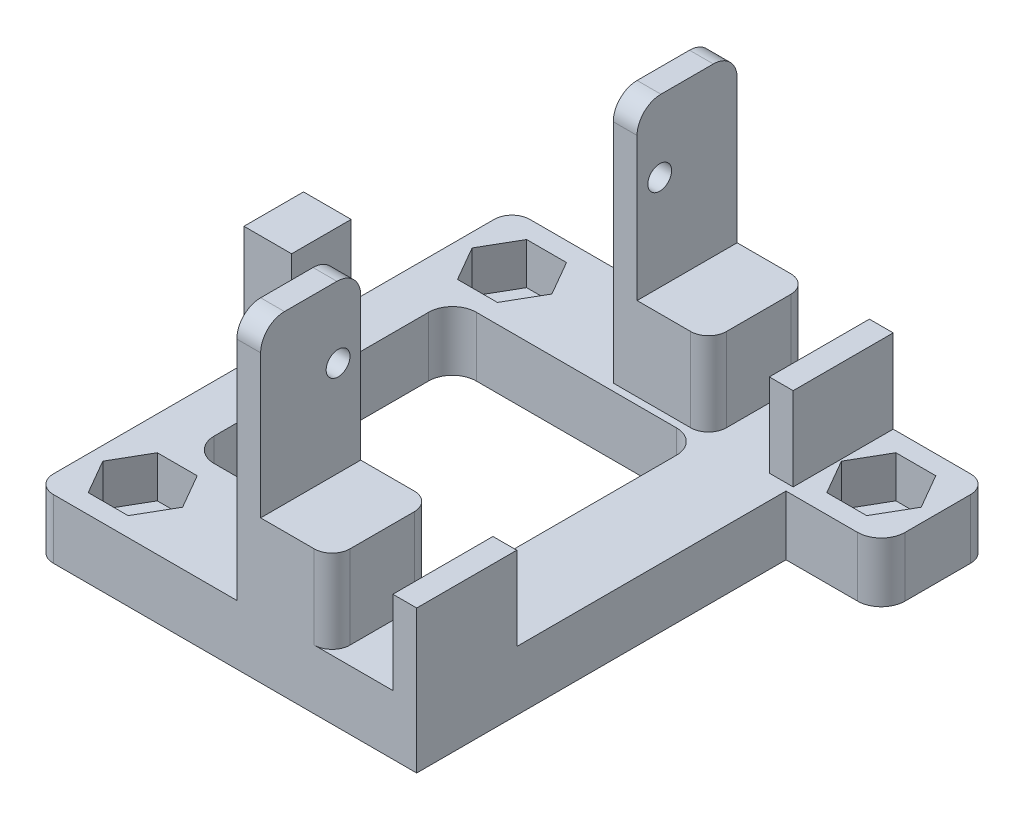
SolidWorks part; units mm, degrees
ref_plane "Plan de face" through (0, 0, 0) normal (0, 0, 1) x (1, 0, 0)
ref_plane "Plan de dessus" through (0, 0, 0) normal (0, 1, 0) x (1, 0, 0)
ref_plane "Plan de droite" through (0, 0, 0) normal (1, 0, 0) x (0, 0, -1)
sketch "Esquisse1" plane through (0, 0, 0) normal (0, 1, 0) x (1, 0, 0)
  circle A0 centre (0, 0) radius 11.75
  dimension "D1" = 23.5
extrude "Boss.-Extru.1" add sketch "Esquisse1" along normal blind 0.0001
sketch "Esquisse2" plane through (0, 0.0001, 0) normal (0, 1, 0) x (1, 0, 0)
  line L1 (-20, -20) -> (20, -20)
  line L2 (-20, -20) -> (-20, 20)
  line L3 (-20, 20) -> (20, 20)
  line L4 (20, -20) -> (20, 20)
  line L5 (-20, -20) -> (20, 20) construction
  line L6 (-20, 20) -> (20, -20) construction
  point P0 (0, 0)
  dimension "D1" = 40
  dimension "D2" = 40
extrude "Boss.-Extru.2" add sketch "Esquisse2" along normal blind 5
sketch "Esquisse3" plane through (0, 5.0001, 0) normal (0, 1, 0) x (1, 0, 0)
  line L0 (-15.5, 15.5) -> (15.5, 15.5) construction
  line L1 (15.5, 15.5) -> (15.5, -15.5) construction
  line L2 (0, 0) -> (-15.5, 0) construction
  line L4 (15.5, -15.5) -> (-15.5, -15.5) construction
  line L6 (-15.5, -15.5) -> (-15.5, 15.5) construction
  line L8 (0, 15.5) -> (0, 0) construction
  line L13 (-13.8257, 12.6) -> (-12.1514, 15.5)
  line L14 (-12.1514, 15.5) -> (-13.8257, 18.4)
  line L15 (-13.8257, 18.4) -> (-17.1743, 18.4)
  line L16 (-17.1743, 18.4) -> (-18.8486, 15.5)
  line L17 (-18.8486, 15.5) -> (-17.1743, 12.6)
  line L18 (-17.1743, 12.6) -> (-13.8257, 12.6)
  line L19 (-18.8486, -15.5) -> (-17.1743, -18.4)
  line L20 (-17.1743, -18.4) -> (-13.8257, -18.4)
  line L21 (-13.8257, -18.4) -> (-12.1514, -15.5)
  line L22 (-12.1514, -15.5) -> (-13.8257, -12.6)
  line L23 (-13.8257, -12.6) -> (-17.1743, -12.6)
  line L24 (-17.1743, -12.6) -> (-18.8486, -15.5)
  line L25 (12.1514, -15.5) -> (13.8257, -18.4)
  line L26 (13.8257, -18.4) -> (17.1743, -18.4)
  line L27 (17.1743, -18.4) -> (18.8486, -15.5)
  line L28 (18.8486, -15.5) -> (17.1743, -12.6)
  line L29 (17.1743, -12.6) -> (13.8257, -12.6)
  line L30 (13.8257, -12.6) -> (12.1514, -15.5)
  line L31 (13.8257, 12.6) -> (17.1743, 12.6)
  line L32 (17.1743, 12.6) -> (18.8486, 15.5)
  line L33 (18.8486, 15.5) -> (17.1743, 18.4)
  line L34 (17.1743, 18.4) -> (13.8257, 18.4)
  line L35 (13.8257, 18.4) -> (12.1514, 15.5)
  line L36 (12.1514, 15.5) -> (13.8257, 12.6)
  circle A4 centre (-15.5, 15.5) radius 2.9 construction
  circle A5 centre (-15.5, -15.5) radius 2.9 construction
  circle A6 centre (15.5, -15.5) radius 2.9 construction
  circle A7 centre (15.5, 15.5) radius 2.9 construction
  point P3 (-13.8931, -18)
  point P5 (-12.6132, -15.5)
  point P6 (12.6132, -15.5)
  point P7 (12.6132, 15.5)
  point P9 (-12.6132, 15.5)
  dimension "D7" = 5.8
  dimension "D8" = 5.8
  dimension "D9" = 5.8
  dimension "D10" = 5.8
  dimension "D2" = 31
  dimension "D3" = 31
  dimension "D4" = 90
  dimension "D5" = 90
extrude "Enlèv. mat.-Extru.1" cut sketch "Esquisse3" against normal blind 3.5
sketch "Esquisse4" plane through (0, 1.5001, 0) normal (0, 1, 0) x (1, 0, 0)
  line L0 (-13.8257, 18.4) -> (-17.1743, 12.6) construction
  line L1 (13.8257, 18.4) -> (17.1743, 12.6) construction
  line L2 (-17.1743, -18.4) -> (-13.8257, -12.6) construction
  line L3 (13.8257, -12.6) -> (17.1743, -18.4) construction
  circle A0 centre (-15.5, 15.5) radius 1.75
  circle A1 centre (15.5, 15.5) radius 1.75
  circle A2 centre (-15.5, -15.5) radius 1.75
  circle A3 centre (15.5, -15.5) radius 1.75
  dimension "D1" = 3.5
  dimension "D2" = 3.5
  dimension "D3" = 3.5
  dimension "D4" = 3.5
extrude "Enlèv. mat.-Extru.2" cut sketch "Esquisse4" against normal blind 2
sketch "Esquisse5" plane through (0, 5.0001, 0) normal (0, 1, 0) x (1, 0, 0)
  line L0 (20, 10.013) -> (12, 10.013) construction
  line L1 (20, -20) -> (20, 20) construction
  line L2 (12, 20) -> (12, -20)
  line L3 (20, 20) -> (-20, 20) construction
  line L4 (-20, -20) -> (20, -20) construction
  line L5 (12, -20) -> (10, -20)
  line L6 (10, -20) -> (10, 20)
  line L7 (10, 20) -> (12, 20)
  line L8 (4.9, 20) -> (-3.1, 20)
  line L9 (-3.1, 20) -> (-3.1, -20)
  line L10 (-3.1, -20) -> (4.9, -20)
  line L11 (4.9, -20) -> (4.9, 20)
  dimension "D1" = 8
  dimension "D2" = 2
  dimension "D3" = 5.1
  dimension "D4" = 8
extrude "Boss.-Extru.3" add sketch "Esquisse5" along normal blind 7
sketch "Esquisse6" plane through (0, 12.0001, 0) normal (0, 1, 0) x (1, 0, 0)
  line L0 (-3.1, -20) -> (4.9, -20) construction
  line L1 (-3.1, 20) -> (-1.1, 20)
  line L2 (-3.1, 20) -> (-3.1, -20)
  line L3 (-3.1, -20) -> (-1.1, -20)
  line L4 (-1.1, 20) -> (-1.1, -20)
  dimension "D1" = 2
extrude "Boss.-Extru.4" add sketch "Esquisse6" along normal blind 14
sketch "Esquisse7" plane through (-1.1, 0, 0) normal (1, 0, 0) x (0, 0, -1)
  line L0 (0, 26.0001) -> (0, 20.0001) construction
  line L1 (-20, 26.0001) -> (20, 26.0001) construction
  line L2 (0, 20.0001) -> (-13.5, 20.0001) construction
  line L3 (0, 20.0001) -> (13.5, 20.0001) construction
  line L4 (0, 26.0001) -> (-11.6, 26.0001)
  line L5 (-11.6, 26.0001) -> (-11.6, 5.0001)
  line L6 (-11.6, 5.0001) -> (11.6, 5.0001)
  line L7 (11.6, 5.0001) -> (11.6, 26.0001)
  line L8 (11.6, 26.0001) -> (0, 26.0001)
  circle A0 centre (-13.5, 20.0001) radius 1
  circle A1 centre (13.5, 20.0001) radius 1
  point P8 (0, 20.0001)
  dimension "D3" = 2
  dimension "D4" = 2
  dimension "D1" = 13.5
  dimension "D2" = 6
  dimension "D5" = 13.5
  dimension "D6" = 11.6
  dimension "D7" = 11.6
  dimension "D8" = 21
extrude "Enlèv. mat.-Extru.3" cut sketch "Esquisse7" against normal blind 14 and the other way blind 14 contours A0 | A1 | L8 L4 L5 L6 L7 region at (-1.1, 20.0001, 13.5) region at (-1.1, 20.0001, -13.5)
fillet "Congé1" radius 2 4 edges at (-2.1, 26.0001, 20) (-2.1, 26.0001, 11.6) (-2.1, 26.0001, -20) (-2.1, 26.0001, -11.6)
fillet "Congé2" radius 1.5 4 edges at (4.9, 8.5001, -20) (4.9, 8.5001, -11.6) (4.9, 8.5001, 11.6) (4.9, 8.5001, 20)
fillet "Congé3" radius 1.5 4 edges at (20, 2.5001, -20) (20, 2.5001, 20) (-20, 2.5001, -20) (-20, 2.5001, 20)
sketch "Esquisse10" plane through (0, 5.0001, 0) normal (0, 1, 0) x (1, 0, 0)
  line L0 (20, -18.5) -> (20, 18.5) construction
  line L1 (12, -20) -> (20, -20)
  line L2 (12, -20) -> (12, 11)
  line L3 (12, 11) -> (20, 11)
  line L4 (20, -20) -> (20, 11)
  dimension "D1" = 31
extrude "Enlèv. mat.-Extru.4" cut sketch "Esquisse10" against normal blind 10
fillet "Congé4" radius 2 1 edges at (20, 2.5001, -11)
sketch "Esquisse11" plane through (0, 5.0001, 0) normal (0, 1, 0) x (1, 0, 0)
  line L0 (-20, 3.0994) -> (-16, 3.0994) construction
  line L1 (-16, -11) -> (4.8, -11)
  line L2 (-16, -11) -> (-16, 11)
  line L3 (-16, 11) -> (4.8, 11)
  line L4 (4.8, -11) -> (4.8, 11)
  line L5 (-20, 18.5) -> (-20, -18.5) construction
  line L6 (-9.2703, 11) -> (-9.2703, 20) construction
  line L8 (4.8, 15.8) -> (10, 15.8)
  line L9 (10, 20) -> (10, 11.6) construction
  line L10 (-3.1, 20) -> (-18.5, 20) construction
  line L11 (-7.9859, -11) -> (-7.9859, -20) construction
  line L12 (-18.5, -20) -> (-3.1, -20) construction
  dimension "D1" = 4
  dimension "D2" = 5.2
  dimension "D3" = 9
  dimension "D4" = 9
extrude "Enlèv. mat.-Extru.5" cut sketch "Esquisse11" against normal blind 10 contours L1 L4 L3 L2 region at (-5.6, 5.0001, 0)
fillet "Congé5" radius 2 4 edges at (4.8, 2.5001, 11) (-16, 2.5001, 11) (4.8, 2.5001, -11) (-16, 2.5001, -11)
sketch "Esquisse12" plane through (0, 5.0001, 0) normal (0, 1, 0) x (1, 0, 0)
  line L0 (-20, 18.5) -> (-20, -18.5) construction
  line L1 (-20, 2.5) -> (-16, 2.5)
  line L2 (-20, 2.5) -> (-20, -2.5)
  line L3 (-20, -2.5) -> (-16, -2.5)
  line L4 (-16, 2.5) -> (-16, -2.5)
  line L5 (-16, -9) -> (-16, 9) construction
  line L6 (-14, 11) -> (2.8, 11) construction
  dimension "D1" = 5
  dimension "D2" = 8.5
extrude "Boss.-Extru.5" add sketch "Esquisse12" along normal blind 10
